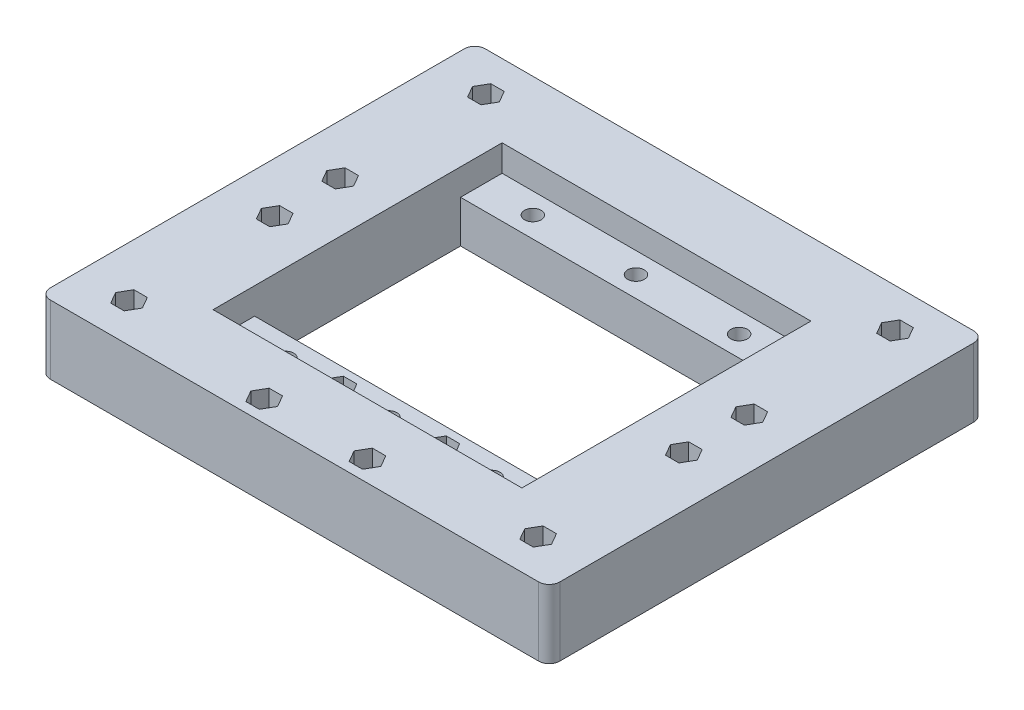
SolidWorks part; units mm, degrees
ref_plane "Front Plane" through (0, 0, 0) normal (0, 0, 1) x (1, 0, 0)
ref_plane "Top Plane" through (0, 0, 0) normal (0, 1, 0) x (1, 0, 0)
ref_plane "Right Plane" through (0, 0, 0) normal (1, 0, 0) x (0, 0, -1)
sketch "Sketch2" plane through (0, 0, 0) normal (0, 1, 0) x (1, 0, 0)
  line L0 (110.49, 95.25) -> (110.49, 60.198) construction
  line L1 (0, 0) -> (122.555, 0)
  line L2 (0, 0) -> (0, 104.648)
  line L3 (0, 104.648) -> (122.555, 104.648)
  line L4 (122.555, 0) -> (122.555, 104.648)
  line L5 (24.13, 27.559) -> (98.425, 27.559)
  line L6 (24.13, 27.559) -> (24.13, 77.089)
  line L7 (24.13, 77.089) -> (98.425, 77.089)
  line L8 (98.425, 27.559) -> (98.425, 77.089)
  line L9 (24.13, 87.089) -> (98.425, 87.089)
  line L10 (24.13, 87.089) -> (24.13, 17.559)
  line L11 (24.13, 17.559) -> (98.425, 17.559)
  line L12 (98.425, 87.089) -> (98.425, 17.559)
  line L13 (110.49, 44.45) -> (110.49, 9.398) construction
  line L14 (73.7447, 22.86) -> (73.7447, 5.08) construction
  line L15 (86.1483, 22.559) -> (61.341, 22.559) construction
  line L16 (61.341, 22.559) -> (61.2775, 0) construction
  circle A0 centre (12.065, 95.25) radius 2
  circle A1 centre (12.065, 60.198) radius 2
  circle A2 centre (12.065, 44.45) radius 2
  circle A3 centre (12.065, 9.398) radius 2
  circle A4 centre (110.49, 9.398) radius 2
  circle A5 centre (110.49, 44.45) radius 2
  circle A6 centre (110.49, 60.198) radius 2
  circle A7 centre (110.49, 95.25) radius 2
  circle A8 centre (36.5337, 82.089) radius 2
  circle A9 centre (61.341, 82.089) radius 2
  circle A10 centre (86.1483, 82.089) radius 2
  circle A11 centre (86.1483, 22.559) radius 2
  circle A12 centre (61.341, 22.559) radius 2
  circle A13 centre (36.5337, 22.559) radius 2
  circle A14 centre (73.7447, 5.08) radius 2
  circle A15 centre (73.7447, 22.86) radius 2
  circle A16 centre (48.9392, 22.9298) radius 2
  circle A17 centre (48.8391, 5.1501) radius 2
  point P41 (110.49, 26.924)
  point P46 (73.7447, 13.97)
  point P47 (73.7447, 22.559)
  dimension "D11" = 4
  dimension "D12" = 4
  dimension "D20" = 35.052
  dimension "D24" = 4
  dimension "D1" = 104.648
  dimension "D2" = 122.555
  dimension "D3" = 17.78
  dimension "D4" = 12.954
  dimension "D5" = 27.559
  dimension "D6" = 27.559
  dimension "D7" = 10
  dimension "D8" = 10
  dimension "D9" = 24.13
  dimension "D10" = 24.13
  dimension "D13" = 12.065
  dimension "D14" = 12.065
  dimension "D15" = 12.4037
  dimension "D16" = 24.8073
  dimension "D17" = 24.8073
  dimension "D18" = 5
  dimension "D19" = 5
  dimension "D21" = 35.052
  dimension "D22" = 9.398
  dimension "D23" = 9.398
extrude "Boss-Extrude5" add sketch "Sketch2" along normal blind 16.51 contours L1 L4 L3 L2 L9 L12 L11 L10 region at (1.6115, 0, -52.324)
extrude "Boss-Extrude7" add sketch "Sketch2<4>" along normal blind 10.16 contours L12 L9 L10 L7 A10 A9 A8 | L12 L5 L10 L11 A13 A12 A11 region at (61.2775, 0, -26.8094) region at (24.8796, 0, -82.089)
sketch "Sketch2<4>" plane through (0, 0, 0) normal (0, 1, 0) x (1, 0, 0) same geometry as "Sketch2"
sketch "Sketch3" plane through (0, 0, 0) normal (0, -1, 0) x (1, 0, 0)
  line L1 (13.6781, -6.604) -> (10.4519, -6.604)
  line L2 (10.4519, -6.604) -> (8.8388, -9.398)
  line L3 (8.8388, -9.398) -> (10.4519, -12.192)
  line L4 (10.4519, -12.192) -> (13.6781, -12.192)
  line L5 (13.6781, -12.192) -> (15.2912, -9.398)
  line L6 (15.2912, -9.398) -> (13.6781, -6.604)
  line L7 (13.6781, -92.456) -> (10.4519, -92.456)
  line L8 (10.4519, -92.456) -> (8.8388, -95.25)
  line L9 (8.8388, -95.25) -> (10.4519, -98.044)
  line L10 (10.4519, -98.044) -> (13.6781, -98.044)
  line L11 (13.6781, -98.044) -> (15.2912, -95.25)
  line L12 (15.2912, -95.25) -> (13.6781, -92.456)
  line L13 (112.1031, -92.456) -> (108.8769, -92.456)
  line L14 (108.8769, -92.456) -> (107.2638, -95.25)
  line L15 (107.2638, -95.25) -> (108.8769, -98.044)
  line L16 (108.8769, -98.044) -> (112.1031, -98.044)
  line L17 (112.1031, -98.044) -> (113.7162, -95.25)
  line L18 (113.7162, -95.25) -> (112.1031, -92.456)
  line L19 (108.8769, -12.192) -> (112.1031, -12.192)
  line L20 (112.1031, -12.192) -> (113.7162, -9.398)
  line L21 (113.7162, -9.398) -> (112.1031, -6.604)
  line L22 (112.1031, -6.604) -> (108.8769, -6.604)
  line L23 (108.8769, -6.604) -> (107.2638, -9.398)
  line L24 (107.2638, -9.398) -> (108.8769, -12.192)
  line L25 (13.6781, -62.992) -> (15.2912, -60.198)
  line L26 (15.2912, -60.198) -> (13.6781, -57.404)
  line L27 (13.6781, -57.404) -> (10.4519, -57.404)
  line L28 (10.4519, -57.404) -> (8.8388, -60.198)
  line L29 (8.8388, -60.198) -> (10.4519, -62.992)
  line L30 (10.4519, -62.992) -> (13.6781, -62.992)
  line L31 (8.8388, -44.45) -> (10.4519, -47.244)
  line L32 (10.4519, -47.244) -> (13.6781, -47.244)
  line L33 (13.6781, -47.244) -> (15.2912, -44.45)
  line L34 (15.2912, -44.45) -> (13.6781, -41.656)
  line L35 (13.6781, -41.656) -> (10.4519, -41.656)
  line L36 (10.4519, -41.656) -> (8.8388, -44.45)
  line L37 (107.2638, -44.45) -> (108.8769, -47.244)
  line L38 (108.8769, -47.244) -> (112.1031, -47.244)
  line L39 (112.1031, -47.244) -> (113.7162, -44.45)
  line L40 (113.7162, -44.45) -> (112.1031, -41.656)
  line L41 (112.1031, -41.656) -> (108.8769, -41.656)
  line L42 (108.8769, -41.656) -> (107.2638, -44.45)
  line L43 (108.8769, -57.404) -> (107.2638, -60.198)
  line L44 (107.2638, -60.198) -> (108.8769, -62.992)
  line L45 (108.8769, -62.992) -> (112.1031, -62.992)
  line L46 (112.1031, -62.992) -> (113.7162, -60.198)
  line L47 (113.7162, -60.198) -> (112.1031, -57.404)
  line L48 (112.1031, -57.404) -> (108.8769, -57.404)
  circle A0 centre (12.065, -9.398) radius 2.794 construction
  circle A1 centre (12.065, -9.398) radius 2 construction
  circle A2 centre (12.065, -9.398) radius 2
  circle A3 centre (12.065, -95.25) radius 2.794 construction
  circle A4 centre (110.49, -95.25) radius 2.794 construction
  circle A5 centre (110.49, -9.398) radius 2.794 construction
  circle A6 centre (110.49, -9.398) radius 2 construction
  circle A7 centre (110.49, -95.25) radius 2 construction
  circle A8 centre (12.065, -95.25) radius 2 construction
  circle A9 centre (110.49, -9.398) radius 2
  circle A10 centre (110.49, -95.25) radius 2
  circle A11 centre (12.065, -95.25) radius 2
  circle A12 centre (12.065, -60.198) radius 2 construction
  circle A13 centre (12.065, -44.45) radius 2 construction
  circle A14 centre (110.49, -44.45) radius 2 construction
  circle A15 centre (110.49, -60.198) radius 2 construction
  circle A16 centre (12.065, -60.198) radius 2
  circle A17 centre (12.065, -44.45) radius 2
  circle A18 centre (110.49, -44.45) radius 2
  circle A19 centre (110.49, -60.198) radius 2
  circle A20 centre (12.065, -60.198) radius 2.794 construction
  circle A21 centre (12.065, -44.45) radius 2.794 construction
  circle A22 centre (110.49, -44.45) radius 2.794 construction
  circle A23 centre (110.49, -60.198) radius 2.794 construction
  dimension "D1" = 5.588
extrude "Cut-Extrude1" cut sketch "Sketch3" along normal blind 6.35 from surface starting at face at (61.2775, 16.51, -52.324)
fillet "Fillet1" radius 2.54 4 edges at (122.555, 8.255, 0) (122.555, 8.255, -104.648) (0, 8.255, -104.648) (0, 8.255, 0)
sketch "Sketch4" plane through (0, 10.16, 0) normal (0, 1, 0) x (1, 0, 0)
  line L1 (39.7599, 22.559) -> (38.1468, 25.353)
  line L2 (38.1468, 25.353) -> (34.9206, 25.353)
  line L3 (34.9206, 25.353) -> (33.3074, 22.559)
  line L4 (33.3074, 22.559) -> (34.9206, 19.765)
  line L5 (34.9206, 19.765) -> (38.1468, 19.765)
  line L6 (38.1468, 19.765) -> (39.7599, 22.559)
  line L7 (58.1148, 22.559) -> (59.7279, 19.765)
  line L8 (59.7279, 19.765) -> (62.9541, 19.765)
  line L9 (62.9541, 19.765) -> (64.5672, 22.559)
  line L10 (64.5672, 22.559) -> (62.9541, 25.353)
  line L11 (62.9541, 25.353) -> (59.7279, 25.353)
  line L12 (59.7279, 25.353) -> (58.1148, 22.559)
  line L13 (82.9221, 22.559) -> (84.5352, 19.765)
  line L14 (84.5352, 19.765) -> (87.7614, 19.765)
  line L15 (87.7614, 19.765) -> (89.3746, 22.559)
  line L16 (89.3746, 22.559) -> (87.7614, 25.353)
  line L17 (87.7614, 25.353) -> (84.5352, 25.353)
  line L18 (84.5352, 25.353) -> (82.9221, 22.559)
  line L19 (82.9221, 82.089) -> (84.5352, 79.295)
  line L20 (84.5352, 79.295) -> (87.7614, 79.295)
  line L21 (87.7614, 79.295) -> (89.3746, 82.089)
  line L22 (89.3746, 82.089) -> (87.7614, 84.883)
  line L23 (87.7614, 84.883) -> (84.5352, 84.883)
  line L24 (84.5352, 84.883) -> (82.9221, 82.089)
  line L25 (64.5672, 82.089) -> (62.9541, 84.883)
  line L26 (62.9541, 84.883) -> (59.7279, 84.883)
  line L27 (59.7279, 84.883) -> (58.1148, 82.089)
  line L28 (58.1148, 82.089) -> (59.7279, 79.295)
  line L29 (59.7279, 79.295) -> (62.9541, 79.295)
  line L30 (62.9541, 79.295) -> (64.5672, 82.089)
  line L31 (39.7599, 82.089) -> (38.1468, 84.883)
  line L32 (38.1468, 84.883) -> (34.9206, 84.883)
  line L33 (34.9206, 84.883) -> (33.3074, 82.089)
  line L34 (33.3074, 82.089) -> (34.9206, 79.295)
  line L35 (34.9206, 79.295) -> (38.1468, 79.295)
  line L36 (38.1468, 79.295) -> (39.7599, 82.089)
  circle A0 centre (36.5337, 22.559) radius 2 construction
  circle A1 centre (61.341, 22.559) radius 2 construction
  circle A2 centre (86.1483, 22.559) radius 2 construction
  circle A3 centre (86.1483, 82.089) radius 2 construction
  circle A4 centre (61.341, 82.089) radius 2 construction
  circle A5 centre (36.5337, 82.089) radius 2 construction
  circle A6 centre (36.5337, 22.559) radius 2
  circle A7 centre (61.341, 22.559) radius 2
  circle A8 centre (86.1483, 22.559) radius 2
  circle A9 centre (86.1483, 82.089) radius 2
  circle A10 centre (61.341, 82.089) radius 2
  circle A11 centre (36.5337, 82.089) radius 2
  circle A12 centre (36.5337, 22.559) radius 2.794 construction
  circle A13 centre (61.341, 22.559) radius 2.794 construction
  circle A14 centre (86.1483, 22.559) radius 2.794 construction
  circle A15 centre (86.1483, 82.089) radius 2.794 construction
  circle A16 centre (61.341, 82.089) radius 2.794 construction
  circle A17 centre (36.5337, 82.089) radius 2.794 construction
  dimension "D1" = 5.588
extrude "Cut-Extrude2" cut sketch "Sketch4" along normal blind 6.35 from surface starting at face at (61.2775, 0, -52.324)
sketch "Sketch5" plane through (0, 10.16, 0) normal (0, 1, 0) x (1, 0, 0)
  line L1 (76.9709, 22.86) -> (75.3578, 25.654)
  line L2 (75.3578, 25.654) -> (72.1316, 25.654)
  line L3 (72.1316, 25.654) -> (70.5184, 22.86)
  line L4 (70.5184, 22.86) -> (72.1316, 20.066)
  line L5 (72.1316, 20.066) -> (75.3578, 20.066)
  line L6 (75.3578, 20.066) -> (76.9709, 22.86)
  line L7 (52.1655, 22.9298) -> (50.5523, 25.7238)
  line L8 (50.5523, 25.7238) -> (47.3261, 25.7238)
  line L9 (47.3261, 25.7238) -> (45.713, 22.9298)
  line L10 (45.713, 22.9298) -> (47.3261, 20.1358)
  line L11 (47.3261, 20.1358) -> (50.5523, 20.1358)
  line L12 (50.5523, 20.1358) -> (52.1655, 22.9298)
  circle A0 centre (73.7447, 22.86) radius 2 construction
  circle A1 centre (48.9392, 22.9298) radius 2 construction
  circle A2 centre (73.7447, 22.86) radius 2
  circle A3 centre (48.9392, 22.9298) radius 2
  circle A4 centre (73.7447, 22.86) radius 2.794 construction
  circle A5 centre (48.9392, 22.9298) radius 2.794 construction
  circle A6 centre (48.8391, 5.1501) radius 2 construction
  circle A7 centre (73.7447, 5.08) radius 2 construction
  circle A8 centre (48.8391, 5.1501) radius 2
  circle A9 centre (73.7447, 5.08) radius 2
  dimension "D1" = 5.588
extrude "Cut-Extrude3" cut sketch "Sketch5" against normal blind 6.35
sketch "Sketch6" plane through (0, 16.51, 0) normal (0, 1, 0) x (1, 0, 0)
  line L1 (70.5184, 5.08) -> (72.1316, 2.286)
  line L2 (72.1316, 2.286) -> (75.3578, 2.286)
  line L3 (75.3578, 2.286) -> (76.9709, 5.08)
  line L4 (76.9709, 5.08) -> (75.3578, 7.874)
  line L5 (75.3578, 7.874) -> (72.1316, 7.874)
  line L6 (72.1316, 7.874) -> (70.5184, 5.08)
  line L7 (45.6129, 5.1501) -> (47.226, 2.3561)
  line L8 (47.226, 2.3561) -> (50.4522, 2.3561)
  line L9 (50.4522, 2.3561) -> (52.0654, 5.1501)
  line L10 (52.0654, 5.1501) -> (50.4522, 7.9441)
  line L11 (50.4522, 7.9441) -> (47.226, 7.9441)
  line L12 (47.226, 7.9441) -> (45.6129, 5.1501)
  circle A0 centre (48.8391, 5.1501) radius 2 construction
  circle A1 centre (73.7447, 5.08) radius 2 construction
  circle A2 centre (48.8391, 5.1501) radius 2
  circle A3 centre (73.7447, 5.08) radius 2
  circle A4 centre (73.7447, 5.08) radius 2.794 construction
  circle A5 centre (48.8391, 5.1501) radius 2.794 construction
  dimension "D1" = 5.588
extrude "Cut-Extrude4" cut sketch "Sketch6" against normal blind 6.35
sketch "Sketch7" plane through (0, 6.35, 0) normal (0, -1, 0) x (1, 0, 0)
  circle A0 centre (36.5337, -82.089) radius 2
  circle A1 centre (61.341, -82.089) radius 2
  circle A2 centre (86.1483, -82.089) radius 2
  circle A3 centre (86.1483, -22.559) radius 2
  circle A4 centre (61.341, -22.559) radius 2
  circle A5 centre (36.5337, -22.559) radius 2
  circle A6 centre (36.5337, -82.089) radius 2 construction
  circle A7 centre (61.341, -82.089) radius 2 construction
  circle A8 centre (86.1483, -82.089) radius 2 construction
  circle A9 centre (86.1483, -22.559) radius 2 construction
  circle A10 centre (61.341, -22.559) radius 2 construction
  circle A11 centre (36.5337, -22.559) radius 2 construction
  circle A12 centre (36.5337, -82.089) radius 2.254
  circle A13 centre (61.341, -82.089) radius 2.254
  circle A14 centre (86.1483, -82.089) radius 2.254
  circle A15 centre (86.1483, -22.559) radius 2.254
  circle A16 centre (61.341, -22.559) radius 2.254
  circle A17 centre (36.5337, -22.559) radius 2.254
  dimension "D1" = 0.254
extrude "Supports - 3D Print" add sketch "Sketch7" along normal up to surface (6.35 mm away) up to face at (61.341, 0, -82.089)
